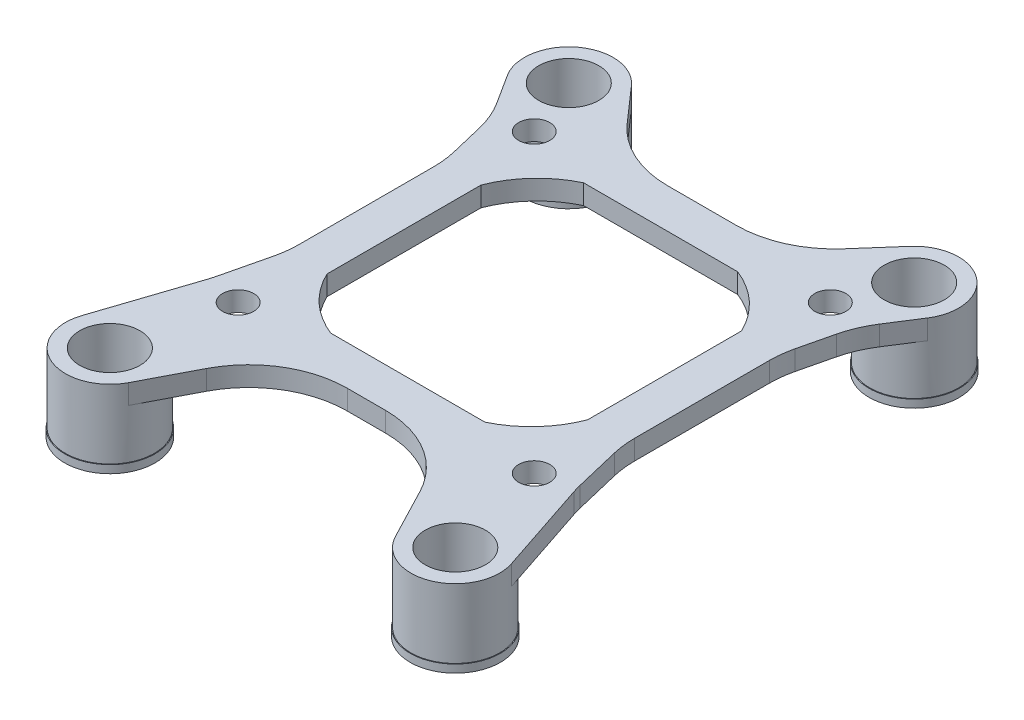
SolidWorks part; units mm, degrees
ref_plane "Front Plane" through (0, 0, 0) normal (0, 0, 1) x (1, 0, 0)
ref_plane "Top Plane" through (0, 0, 0) normal (0, 1, 0) x (1, 0, 0)
ref_plane "Right Plane" through (0, 0, 0) normal (1, 0, 0) x (0, 0, -1)
sketch "Sketch1" plane through (0, 0, 0) normal (0, 1, 0) x (1, 0, 0)
  line L0 (0, 0) -> (-17.5, 0) construction
  line L1 (17.5, 23.25) -> (-17.5, 23.25) construction
  line L2 (17.5, 23.25) -> (17.5, -23.25) construction
  line L3 (17.5, -23.25) -> (-17.5, -23.25) construction
  line L4 (-17.5, 23.25) -> (-17.5, -23.25) construction
  line L5 (17.5, 23.25) -> (-17.5, -23.25) construction
  line L6 (17.5, -23.25) -> (-17.5, 23.25) construction
  line L7 (0, 0) -> (0, 23.25) construction
  circle A0 centre (-17.5, 23.25) radius 1.575
  circle A1 centre (-17.5, 23.25) radius 4.575
  circle A2 centre (17.5, 23.25) radius 1.575
  circle A3 centre (17.5, 23.25) radius 4.575
  circle A4 centre (-17.5, -23.25) radius 4.575
  circle A5 centre (-17.5, -23.25) radius 1.575
  circle A6 centre (17.5, -23.25) radius 1.575
  circle A7 centre (17.5, -23.25) radius 4.575
  point P0 (0, 0)
  dimension "D3" = 3.15
  dimension "D4" = 3
  dimension "D1" = 46.5
  dimension "D2" = 35
extrude "Boss-Extrude1" add sketch "Sketch1" along normal blind 0.8
sketch "Sketch2" plane through (0, 0.8, 0) normal (0, 1, 0) x (1, 0, 0)
  line L0 (0, 0) -> (0, 27.0836) construction
  line L1 (0, 0) -> (-45.1618, 0) construction
  circle A0 centre (-17.5, 23.25) radius 4.5
  circle A1 centre (-17.5, 23.25) radius 3.05
  circle A2 centre (17.5, 23.25) radius 3.05
  circle A3 centre (17.5, 23.25) radius 4.5
  circle A4 centre (17.5, -23.25) radius 4.5
  circle A5 centre (17.5, -23.25) radius 3.05
  circle A6 centre (-17.5, -23.25) radius 3.05
  circle A7 centre (-17.5, -23.25) radius 4.5
  dimension "D1" = 9
  dimension "D2" = 6.1
extrude "Boss-Extrude2" add sketch "Sketch2" along normal blind 5
sketch "Sketch3" plane through (0, 5.8, 0) normal (0, 1, 0) x (1, 0, 0)
  line L0 (0, 0) -> (0, -11.6847) construction
  line L1 (0, 2.25) -> (-15, 2.25) construction
  line L2 (15, 17.25) -> (-15, 17.25) construction
  line L3 (15, 17.25) -> (15, -12.75) construction
  line L4 (15, -12.75) -> (-15, -12.75) construction
  line L5 (-15, 17.25) -> (-15, -12.75) construction
  line L6 (15, 17.25) -> (-15, -12.75) construction
  line L7 (15, -12.75) -> (-15, 17.25) construction
  line L8 (-18.4767, 16.4175) -> (-17, 10.25)
  line L9 (-17, 10.25) -> (-17, -5.75)
  line L10 (-18.4767, 16.4175) -> (-21.2929, 20.8284)
  line L11 (-13, 10.25) -> (-13, -5.75)
  line L12 (-11.5233, 16.4175) -> (-13, 10.25)
  line L13 (-8, 15.25) -> (8, 15.25)
  line L14 (-8, 19.25) -> (8, 19.25)
  line L15 (-11.5233, -11.9175) -> (-13, -5.75)
  line L16 (-14.1675, 13.7733) -> (-8, 15.25)
  line L17 (-14.1184, 26.2189) -> (-8, 19.25)
  line L18 (-18.4767, -11.9175) -> (-17, -5.75)
  line L19 (-14.1675, -9.2733) -> (-8, -10.75)
  line L20 (-8, -10.75) -> (8, -10.75)
  line L21 (-18.4767, -11.9175) -> (-21.7705, -21.8312)
  line L22 (0, 0) -> (-32.9553, 0) construction
  line L23 (-8, -14.75) -> (8, -14.75)
  line L24 (-8, -14.75) -> (-13.5088, -25.3285)
  line L25 (8, -14.75) -> (13.5088, -25.3285)
  line L26 (18.4767, -11.9175) -> (21.7705, -21.8312)
  line L27 (14.1675, -9.2733) -> (8, -10.75)
  line L28 (18.4767, -11.9175) -> (17, -5.75)
  line L29 (14.1184, 26.2189) -> (8, 19.25)
  line L30 (14.1675, 13.7733) -> (8, 15.25)
  line L31 (11.5233, -11.9175) -> (13, -5.75)
  line L32 (11.5233, 16.4175) -> (13, 10.25)
  line L33 (13, 10.25) -> (13, -5.75)
  line L34 (18.4767, 16.4175) -> (21.2929, 20.8284)
  line L35 (17, 10.25) -> (17, -5.75)
  line L36 (18.4767, 16.4175) -> (17, 10.25)
  circle A0 centre (-15, -12.75) radius 1.575
  circle A1 centre (-15, -12.75) radius 3.575
  circle A3 centre (-17.5, 23.25) radius 4.5 construction
  circle A7 centre (-17.5, 23.25) radius 4.5
  circle A8 centre (-17.5, 23.25) radius 3.05 construction
  circle A9 centre (-17.5, 23.25) radius 3.05
  circle A10 centre (-17.5, -23.25) radius 3.05
  circle A11 centre (-17.5, -23.25) radius 4.5
  circle A12 centre (15, 17.25) radius 3.575
  circle A16 centre (-15, 17.25) radius 1.575
  circle A17 centre (-15, 17.25) radius 3.575
  circle A18 centre (15, 17.25) radius 1.575
  circle A19 centre (17.5, -23.25) radius 4.5
  circle A20 centre (17.5, -23.25) radius 3.05
  circle A21 centre (17.5, 23.25) radius 3.05
  circle A22 centre (17.5, 23.25) radius 4.5
  circle A23 centre (15, -12.75) radius 3.575
  circle A24 centre (15, -12.75) radius 1.575
  point P1 (0, 2.25)
  point P27 (0, 15.25)
  point P33 (-13, 2.25)
  point P36 (-17, 2.25)
  point P60 (17, 2.25)
  point P61 (13, 2.25)
  point P64 (0, -14.75)
  point P67 (0, -10.75)
  point P75 (0, 19.25)
  circle M31 centre (-17.5, -23.25) radius 4.5
  circle M32 centre (-17.5, -23.25) radius 3.05
  dimension "D2" = 3.15
  dimension "D4" = 2
  dimension "D1" = 30
  dimension "D3" = 2.25
  dimension "D5" = 4
  dimension "D6" = 8
extrude "Boss-Extrude3" add sketch "Sketch3" along normal blind 2 contours M31 M32 | A23 L31 L27 L20 L19 L15 A1 L21 L24 L23 L25 A19 L26 M31 | A19 A20 | A1 A0 | A23 A24 | A23 L28 L35 L36 A12 L30 L32 L33 L31 L27 | A17 L8 L9 L18 A1 L19 L15 L11 L12 L16 | A17 A7 A16 | A17 L16 L12 | A12 A22 L29 L14 L17 A7 A17 L12 L16 L13 L30 L32 | A17 A7 L10 | A17 A7 A9 | L30 A12 L32 | A12 A22 A18 | A7 A17 | A22 A12 | A22 A12 A21 | L34 A22 A12 | A23 L27 L31 | L19 A1 L15 region at (-15.0418, 5.8, -2.25) region at (-18.455, 5.8, -17.6243) region at (-19.2539, 5.8, -18.4492) region at (-20.1269, 5.8, -26.7463) region at (-12.3763, 5.8, -14.6263) region at (-16.0587, 5.8, -19.7909) region at (0, 5.8, -18.1375) region at (-15.4733, 5.8, 16.7595) region at (-16.8169, 5.8, 9.7891) region at (-16.8017, 5.8, 18.9334) region at (-12.3763, 5.8, 10.1263) region at (19.0416, 5.8, -27.3424) region at (12.3763, 5.8, -14.6263) region at (15.0418, 5.8, -2.25) region at (15.7309, 5.8, -19.0041) region at (16.0587, 5.8, -19.7909) region at (19.2539, 5.8, -18.4492) region at (15.7954, 5.8, 19.2232) region at (12.3763, 5.8, 10.1263) region at (16.8169, 5.8, 9.7891)
fillet "Fillet1" radius 10 16 edges at (-18.4767, 6.8, 11.9175) (-17, 6.8, 5.75) (-17, 6.8, -10.25) (-18.4767, 6.8, -16.4175) (12.0341, 6.8, 9.7841) (-12.0341, 6.8, 9.7841) (12.0341, 6.8, -14.2841) (-12.0341, 6.8, -14.2841) (-8, 6.8, -19.25) (8, 6.8, -19.25) (18.4767, 6.8, -16.4175) (17, 6.8, -10.25) (17, 6.8, 5.75) (18.4767, 6.8, 11.9175) (8, 6.8, 14.75) (-8, 6.8, 14.75)
